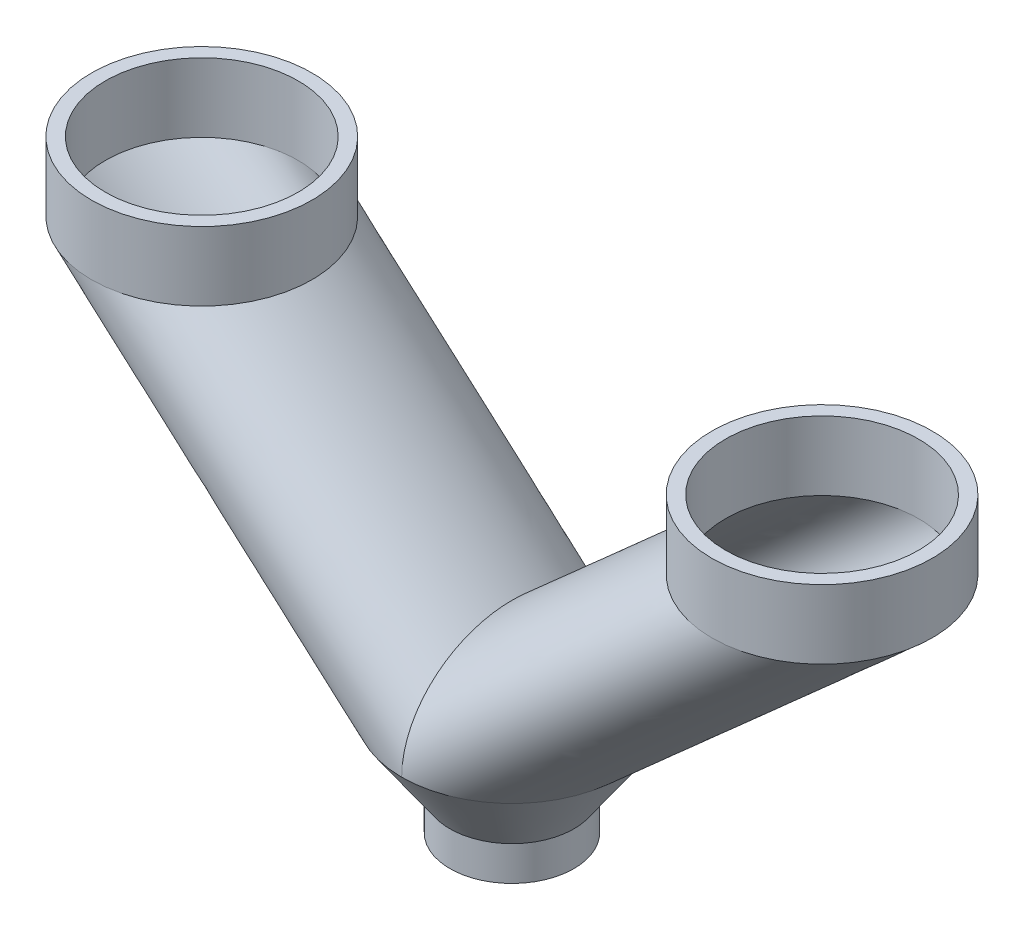
SolidWorks part; units mm, degrees
ref_plane "Alzado" through (0, 0, 0) normal (0, 0, 1) x (1, 0, 0)
ref_plane "Planta" through (0, 0, 0) normal (0, 1, 0) x (1, 0, 0)
ref_plane "Vista lateral" through (0, 0, 0) normal (1, 0, 0) x (0, 0, -1)
sketch "Croquis18" plane through (0, 0, 0) normal (0, 1, 0) x (1, 0, 0)
  line L0 (0, 0) -> (-90, 0) construction
  circle A0 centre (0, 0) radius 14
  circle A1 centre (-90, 0) radius 14
  circle A2 centre (0, 0) radius 16
  circle A3 centre (-90, 0) radius 16
  dimension "D2" = 28
  dimension "D3" = 2
  dimension "D4" = 28
  dimension "D5" = 2
  dimension "D1" = 90
extrude "Saliente-Extruir3" add sketch "Croquis18" along normal blind 10
sketch "Croquis19" plane through (0, 0, 0) normal (0, 0, 1) x (1, 0, 0)
  line L0 (-90, 0) -> (0, 0) construction
  line L1 (-106, 0) -> (-74, 0) construction
  line L2 (-45, 0) -> (-45, -40) construction
  line L3 (-90, 0) -> (-45, -40)
  dimension "D1" = 40
  dimension "D2" = 45
sketch "Croquis20" plane through (0, 0, 0) normal (0, 0, 1) x (1, 0, 0)
  line L0 (0, 0) -> (-45, -40)
ref_plane "Plano1" through (0, -40, 0) normal (0, 1, 0) x (1, 0, 0)
sketch "Croquis21" plane through (0, -40, 0) normal (0, 1, 0) x (1, 0, 0)
  line L0 (-90, 0) -> (0, 0) construction
  circle A0 centre (-45, 0) radius 14
  circle A1 centre (-45, 0) radius 16
  dimension "D1" = 2
  dimension "D2" = 28
sketch "Croquis23" plane through (0, -40, 0) normal (0, 1, 0) x (1, 0, 0)
  circle A0 centre (-45, 0) radius 14
  circle A1 centre (-45, 0) radius 16
  dimension "D1" = 2
  dimension "D2" = 28
sweep "Barrer1" add profiles "Croquis21" path "Croquis19"
sweep "Barrer2" add profiles "Croquis23" path "Croquis20"
sketch "Croquis25" plane through (0, -40, 0) normal (0, -1, 0) x (1, 0, 0)
  circle A0 centre (-45, 0) radius 14
sweep "Cortar-Barrer1" cut profiles "Croquis25" path "Croquis20<2>"
sketch "Croquis20<2>" plane through (0, 0, 0) normal (0, 0, 1) x (1, 0, 0) same geometry as "Croquis20"
sweep "Cortar-Barrer2" cut profiles "Croquis25<2>" path "Croquis19<2>"
sketch "Croquis25<2>" plane through (0, -40, 0) normal (0, -1, 0) x (1, 0, 0) same geometry as "Croquis25"
sketch "Croquis19<2>" plane through (0, 0, 0) normal (0, 0, 1) x (1, 0, 0) same geometry as "Croquis19"
sketch "Croquis29" plane through (0, 0, 0) normal (0, 0, 1) x (1, 0, 0)
  line L0 (-61, -40) -> (-59, -40)
  line L2 (-59, -40) -> (-52, -50)
  line L3 (-52, -50) -> (-54, -50)
  line L4 (-54, -50) -> (-61, -40)
  dimension "D1" = 2
  dimension "D2" = 10
  dimension "D3" = 7
  dimension "D4" = 14
sketch "Croquis30" plane through (0, 0, 0) normal (0, 0, 1) x (1, 0, 0)
  line L0 (-45, -40) -> (-45, -50.2967)
revolve "Revolución2" add sketch "Croquis29" angle 360 about L0
sketch "Croquis31" plane through (0, -50, 0) normal (0, -1, 0) x (1, 0, 0)
  line L0 (-45, 13.9748) -> (-45, -13.9787) construction
  circle A0 centre (-45, -0.002) radius 6.998
  circle A1 centre (-45, -0.002) radius 8.998
extrude "Saliente-Extruir4" add sketch "Croquis31" along normal blind 5
